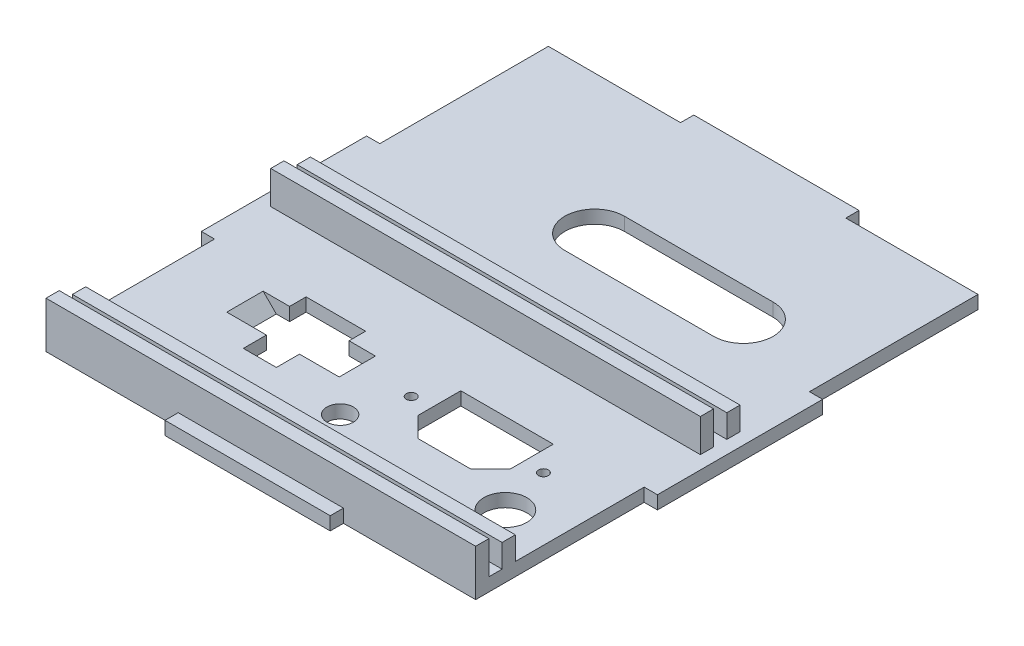
SolidWorks part; units mm, degrees
ref_plane "Front Plane" through (0, 0, 0) normal (0, 0, 1) x (1, 0, 0)
ref_plane "Top Plane" through (0, 0, 0) normal (0, 1, 0) x (1, 0, 0)
ref_plane "Right Plane" through (0, 0, 0) normal (1, 0, 0) x (0, 0, -1)
sketch "Sketch3" plane through (0, 0, 0) normal (0, 1, 0) x (1, 0, 0)
  line L24 (-25, 80) -> (25, 80)
  line L25 (69, 25) -> (69, -25)
  line L26 (25, -80) -> (-25, -80)
  line L27 (-69, -25) -> (-69, 25)
  line L28 (-65, 76) -> (-25, 76)
  line L29 (-25, 76) -> (-25, 80)
  line L30 (25, 80) -> (25, 76)
  line L31 (25, 76) -> (65, 76)
  line L32 (-65, -76) -> (-25, -76)
  line L33 (-25, -76) -> (-25, -80)
  line L34 (25, -76) -> (25, -80)
  line L35 (25, -76) -> (65, -76)
  line L36 (-69, 25) -> (-65, 25)
  line L37 (-65, 25) -> (-65, 76)
  line L38 (-69, -25) -> (-65, -25)
  line L39 (-65, -25) -> (-65, -76)
  line L40 (65, 76) -> (65, 25)
  line L41 (65, 25) -> (69, 25)
  line L42 (65, -76) -> (65, -25)
  line L43 (65, -25) -> (69, -25)
  dimension "D2" = 160
  dimension "D3" = 50
  dimension "D4" = 69
  dimension "D5" = 25
  dimension "D6" = 4
  dimension "D7" = 4
  dimension "D8" = 4
  dimension "D9" = 4
  dimension "D10" = 50
  dimension "D11" = 25
  dimension "D12" = 50
  dimension "D13" = 25
  dimension "D14" = 4
  dimension "D15" = 69
  dimension "D16" = 50
  dimension "D17" = 80
  dimension "D18" = 4
  dimension "D19" = 4
  dimension "D20" = 25
extrude "Boss-Extrude1" add sketch "Sketch3" along normal blind 4
sketch "Sketch4" plane through (0, 4, 0) normal (0, 1, 0) x (1, 0, 0)
  line L0 (-65, -76) -> (65, -76)
  line L1 (65, -76) -> (65, -72)
  line L2 (65, -76) -> (65, -25) construction
  line L3 (65, -72) -> (-65, -72)
  line L4 (-65, -25) -> (-65, -76) construction
  line L5 (-65, -72) -> (-65, -76)
  dimension "D1" = 4
extrude "Boss-Extrude2" add sketch "Sketch4" along normal blind 10
sketch "Sketch5" plane through (0, 4, 0) normal (0, 1, 0) x (1, 0, 0)
  line L0 (-65, -68) -> (-65, -64)
  line L1 (-65, -25) -> (-65, -72) construction
  line L2 (-65, -64) -> (65, -64)
  line L3 (65, -72) -> (65, -25) construction
  line L4 (65, -64) -> (65, -68)
  line L5 (65, -68) -> (-65, -68)
  line L6 (65, -72) -> (-65, -72) construction
  dimension "D1" = 4
  dimension "D2" = 4
extrude "Boss-Extrude3" add sketch "Sketch5" along normal blind 7
sketch "Sketch6" plane through (0, 4, 0) normal (0, 1, 0) x (1, 0, 0)
  line L0 (-65, -4) -> (-65, -8)
  line L1 (-65, 76) -> (-65, 25) construction
  line L2 (-65, -8) -> (65, -8)
  line L3 (65, 25) -> (65, 76) construction
  line L4 (-65, -4) -> (65, -4)
  line L5 (65, -4) -> (65, -8)
  line L6 (65, -64) -> (-65, -64) construction
  dimension "D1" = 4
  dimension "D2" = 56
extrude "Boss-Extrude4" add sketch "Sketch6" along normal blind 10
sketch "Sketch8" plane through (0, 4, 0) normal (0, 1, 0) x (1, 0, 0)
  line L0 (-65, 4) -> (-65, 0)
  line L1 (-65, 76) -> (-65, 25) construction
  line L2 (-65, 0) -> (65, 0)
  line L3 (65, 25) -> (65, 76) construction
  line L4 (65, 0) -> (65, 4)
  line L5 (65, 4) -> (-65, 4)
  line L6 (65, -4) -> (-65, -4) construction
  dimension "D1" = 4
  dimension "D2" = 4
extrude "Boss-Extrude5" add sketch "Sketch8" along normal blind 7
sketch "Sketch9" plane through (0, 4, 0) normal (0, 1, 0) x (1, 0, 0)
  line L0 (-22, -49.3) -> (-32, -49.3)
  line L1 (-32, -49.3) -> (-32, -42.3)
  line L2 (-32, -42.3) -> (-40, -42.3)
  line L3 (-40, -42.3) -> (-40, -31.3)
  line L4 (-40, -31.3) -> (-36, -31.3)
  line L5 (-36, -31.3) -> (-36, -26.3)
  line L6 (-36, -26.3) -> (-18, -26.3)
  line L7 (-18, -26.3) -> (-18, -31.3)
  line L8 (-18, -31.3) -> (-14, -31.3114)
  line L9 (-14, -31.3114) -> (-14, -42.2886)
  line L10 (-14, -42.2886) -> (-22, -42.3)
  line L11 (-22, -42.3) -> (-22, -49.3)
  line L12 (65, -64) -> (-65, -64) construction
  line L13 (-65, -25) -> (-65, -64) construction
  point P15 (-27, -26.3)
  point P16 (-27, -49.3)
  point P17 (-40, -36.8)
  point P18 (-14, -36.8)
  dimension "D1" = 18
  dimension "D2" = 11
  dimension "D3" = 10
  dimension "D4" = 26
  dimension "D5" = 23
  dimension "D6" = 5
  dimension "D7" = 4
  dimension "D8" = 4
  dimension "D9" = 14.7
  dimension "D10" = 25
  dimension "D11" = 7
  dimension "D12" = 7
  dimension "D13" = 8
extrude "Cut-Extrude1" cut sketch "Sketch9" against normal through all
chamfer "Chamfer2" distance 4 angle 45 1 edges at (-40, 4, 36.8)
chamfer "Chamfer3" distance 4 angle 45 1 edges at (-14, 4, 36.8)
sketch "Sketch11" plane through (0, 4, 0) normal (0, 1, 0) x (1, 0, 0)
  line L0 (12, -27.5) -> (40, -27.5)
  line L1 (40, -27.5) -> (40, -40.5)
  line L2 (34, -46.5) -> (18, -46.5)
  line L3 (12, -40.5) -> (12, -27.5)
  line L4 (34, -46.5) -> (40, -40.5)
  line L5 (18, -46.5) -> (12, -40.5)
  line L6 (65, -64) -> (-65, -64) construction
  line L7 (65, -64) -> (65, -25) construction
  dimension "D1" = 28
  dimension "D2" = 19
  dimension "D3" = 45
  dimension "D4" = 45
  dimension "D5" = 13
  dimension "D6" = 13
  dimension "D7" = 17.5
  dimension "D8" = 25
extrude "Cut-Extrude3" cut sketch "Sketch11" against normal through all
sketch "Sketch12" plane through (0, 4, 0) normal (0, 1, 0) x (1, 0, 0)
  line L0 (12, -27.5) -> (12, -40.5) construction
  line L1 (40, -40.5) -> (40, -27.5) construction
  line L2 (40, -27.5) -> (12, -27.5) construction
  circle A0 centre (6, -36.5) radius 1.5
  circle A1 centre (46, -36.5) radius 1.5
  dimension "D1" = 3
  dimension "D2" = 3
  dimension "D3" = 6
  dimension "D4" = 6
  dimension "D5" = 9
extrude "Cut-Extrude4" cut sketch "Sketch12" against normal through all
sketch "Sketch13" plane through (0, 4, 0) normal (0, 1, 0) x (1, 0, 0)
  line L0 (65, -64) -> (-65, -64) construction
  line L1 (65, -64) -> (65, -25) construction
  circle A0 centre (50, -52) radius 6.5
  dimension "D1" = 13
  dimension "D2" = 12
  dimension "D3" = 15
extrude "Cut-Extrude5" cut sketch "Sketch13" against normal through all
sketch "Sketch14" plane through (0, 4, 0) normal (0, 1, 0) x (1, 0, 0)
  line L0 (65, -64) -> (-65, -64) construction
  circle A0 centre (0, -52) radius 4
  dimension "D1" = 8
  dimension "D2" = 12
extrude "Cut-Extrude6" cut sketch "Sketch14" against normal through all
sketch "Sketch15" plane through (0, 0, 0) normal (0, -1, 0) x (1, 0, 0)
  line L0 (-9, -25) -> (36, -25)
  line L1 (36, -43) -> (-9, -43)
  line L2 (-25, 80) -> (25, 80) construction
  line L3 (-69, -25) -> (-69, 25) construction
  arc A0 (-9, -25) -> (-9, -43) centre (-9, -34) ccw
  arc A1 (36, -43) -> (36, -25) centre (36, -34) ccw
  point P10 (-9, -43)
  point P11 (0, 0)
  dimension "D1" = 18
  dimension "D2" = 18
  dimension "D3" = 45
  dimension "D4" = 114
  dimension "D5" = 60
extrude "Cut-Extrude7" cut sketch "Sketch15" against normal blind 10
